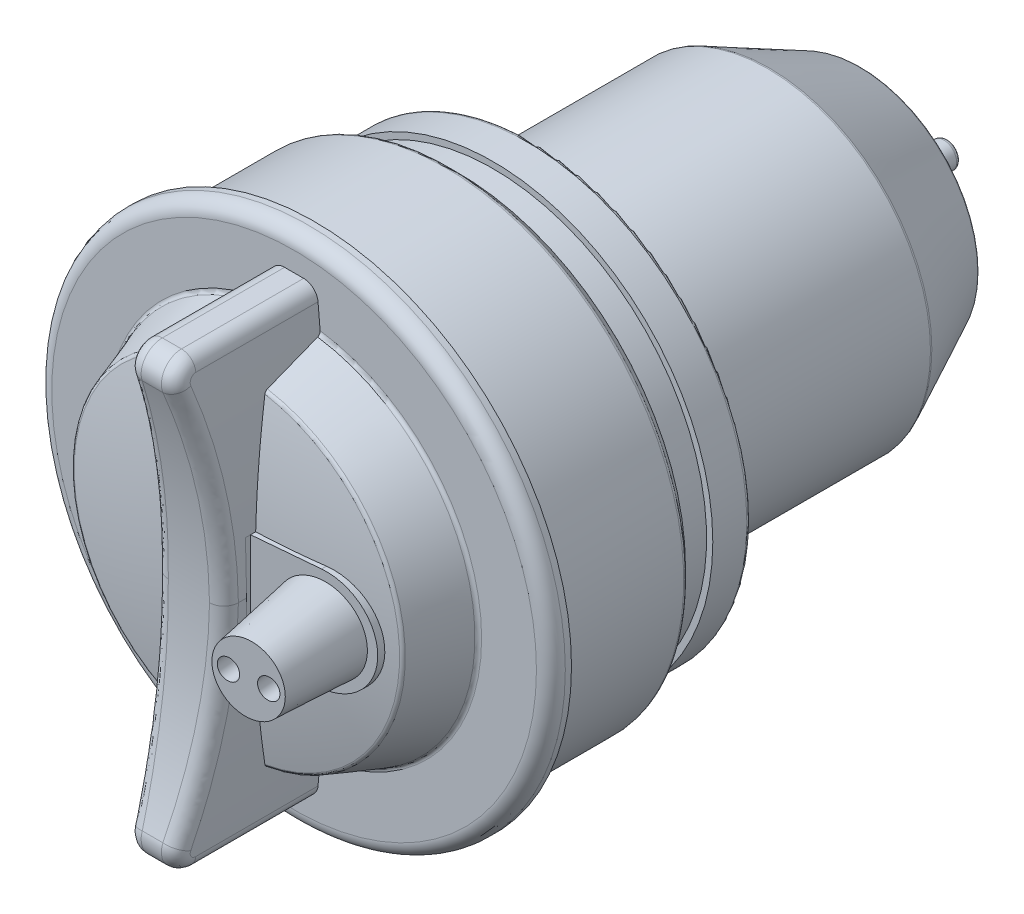
SolidWorks part; units mm, degrees
ref_plane "Front Plane" through (0, 0, 0) normal (0, 0, 1) x (1, 0, 0)
ref_plane "Top Plane" through (0, 0, 0) normal (0, 1, 0) x (1, 0, 0)
ref_plane "Right Plane" through (0, 0, 0) normal (1, 0, 0) x (0, 0, -1)
sketch "Sketch1" plane through (0, 0, 0) normal (0, 0, 1) x (1, 0, 0)
  circle A0 centre (0, 0) radius 20.066
  dimension "D1" = 40.132
extrude "Boss-Extrude1" add sketch "Sketch1" along normal blind 40.64
chamfer "Chamfer1" distance 5.588 distance2 11.43 1 edges at (20.066, 0, 0) first distance on face at (20.066, 0, 0)
sketch "Sketch3" plane through (0, 0, 40.64) normal (0, 0, 1) x (1, 0, 0)
  circle A0 centre (0, 0) radius 26.289
  dimension "D1" = 52.578
extrude "Boss-Extrude2" add sketch "Sketch3" along normal blind 8.89
sketch "Sketch4" plane through (0, 0, 40.64) normal (0, 0, -1) x (-1, 0, 0)
  circle A0 centre (0, 0) radius 24.003
  circle A1 centre (0, 0) radius 20.066
  dimension "D1" = 48.006
  dimension "D2" = 40.132
extrude "Cut-Extrude1" cut sketch "Sketch4" against normal blind 1.778
sketch "Sketch5" plane through (0, 0, 40.64) normal (0, 0, -1) x (-1, 0, 0)
  circle A0 centre (0, 0) radius 27.051
  circle A1 centre (0, 0) radius 26.289
  dimension "D1" = 54.102
extrude "Boss-Extrude3" add sketch "Sketch5" against normal blind 4.699
sketch "Sketch6" plane through (0, 0, 49.53) normal (0, 0, 1) x (1, 0, 0)
  circle A0 centre (0, 0) radius 29.4005
  dimension "D1" = 58.801
extrude "Boss-Extrude4" add sketch "Sketch6" along normal blind 17.78
chamfer "Chamfer2" distance 1.524 angle 45 1 edges at (29.4005, 0, 49.53)
sketch "Sketch8" plane through (0, 0, 67.31) normal (0, 0, 1) x (1, 0, 0)
  circle A0 centre (0, 0) radius 31.623
  dimension "D1" = 63.246
extrude "Boss-Extrude5" add sketch "Sketch8" along normal blind 2.54
fillet "Fillet1" radius 1.778 1 edges at (31.623, 0, 69.85)
sketch "Sketch9" plane through (0, 0, 0) normal (1, 0, 0) x (0, 0, -1)
  line L0 (-69.85, 0) -> (-69.85, -22.733)
  line L1 (-69.85, 31.623) -> (-69.85, -31.623) construction
  line L2 (-69.85, -22.733) -> (-76.835, -20.32)
  line L4 (-78.994, 0) -> (-69.85, 0)
  spline S0 degree 2 poles (-78.994, 0) (-79.1044, -10.2687) (-76.835, -20.32) knots 0 0 0 1 1 1
  dimension "D1" = 22.733
  dimension "D2" = 20.32
  dimension "D3" = 9.144
  dimension "D4" = 6.985
revolve "Revolve1" add sketch "Sketch9" angle 360 about L4
sketch "Sketch10" plane through (0, 0, 69.85) normal (0, 0, 1) x (1, 0, 0)
  line L0 (0, -39.5889) -> (0, 36.9015) construction
  line L1 (-2.794, 27.432) -> (2.794, 27.432)
  line L2 (0, 0) -> (-18.8505, 0) construction
  line L3 (-2.794, -27.432) -> (2.794, -27.432)
  circle A0 centre (0, 0) radius 31.623 construction
  spline S0 degree 2 poles (-4.318, 0) (-4.1228, 13.7514) (-2.794, 27.432) knots 0 0 0 1 1 1
  spline S1 degree 2 poles (-4.318, 0) (-4.1228, -13.7514) (-2.794, -27.432) knots 0 0 0 1 1 1
  spline S2 degree 2 poles (4.318, 0) (4.1228, -13.7514) (2.794, -27.432) knots 0 0 0 1 1 1
  spline S3 degree 2 poles (4.318, 0) (4.1228, 13.7514) (2.794, 27.432) knots 0 0 0 1 1 1
  point P16 (0, 27.432)
  point P17 (0, -27.432)
  dimension "D1" = 4.318
  dimension "D2" = 2.794
  dimension "D3" = 3.556
  dimension "D4" = 27.432
extrude "Boss-Extrude6" add sketch "Sketch10" along normal blind 18.796
sketch "Sketch11" plane through (0, 0, 0) normal (1, 0, 0) x (0, 0, -1)
  line L0 (-88.646, 0) -> (-78.9348, 0) construction
  line L1 (-88.646, -27.432) -> (-69.85, -27.432) construction
  line L2 (-88.646, 0) -> (-88.646, -27.432) construction
  line L3 (-88.646, 27.432) -> (-88.646, -27.432)
  spline S0 degree 2 poles (-88.646, 27.432) (-76.962, 0) (-88.646, -27.432) knots 0 0 0 1 1 1
  dimension "D1" = 5.842
extrude "Cut-Extrude2" cut sketch "Sketch11" against normal mid plane 18.796
fillet "Fillet2" radius 2.54 2 edges at (0, -27.432, 88.646) (0, 27.432, 88.646)
fillet "Fillet3" radius 1.778 12 edges at (-2.794, -27.432, 77.3737) (-2.907, -26.2471, 87.0458) (-2.794, 27.432, 77.3737) (-2.8881, 26.4479, 86.9051) (2.794, -27.432, 77.3737) (2.8881, -26.4479, 86.9051) (2.794, 27.432, 77.3737) (2.907, 26.2471, 87.0458) (-3.72, -15.7702, 84.7347) (-4.1494, 6.8747, 83.1709) (4.1494, -6.8747, 83.1709) (3.72, 15.7702, 84.7347)
fillet "Fillet4" radius 0.508 4 edges at (22.733, 0, 69.85) (-22.733, 0, 69.85) (-20.32, 0, 76.835) (20.32, 0, 76.835)
sketch "Sketch12" plane through (0, 0, 69.85) normal (0, 0, 1) x (1, 0, 0)
  line L0 (12.192, 6.35) -> (1.0967, 6.35)
  line L1 (1.0967, 6.35) -> (1.0967, -6.35)
  line L2 (1.0967, -6.35) -> (12.192, -6.35)
  arc A0 (12.192, -6.35) -> (12.192, 6.35) centre (12.192, 0) ccw
  dimension "D1" = 12.7
  dimension "D2" = 12.192
extrude "Boss-Extrude7" add sketch "Sketch12" along normal blind 10.16
sketch "Sketch13" plane through (0, 0, 0) normal (0, 1, 0) x (1, 0, 0)
  line L0 (4.1673, -80.01) -> (4.1673, -79.3789)
  line L1 (4.1673, -78.7479) -> (4.1673, -80.01) construction
  line L2 (4.1673, -79.3789) -> (19.0286, -78.0506)
  line L3 (19.0286, -78.0506) -> (19.2038, -80.01)
  line L4 (19.2038, -80.01) -> (4.1673, -80.01)
extrude "Cut-Extrude3" cut sketch "Sketch13" against normal mid plane 15.24
sketch "Sketch14" plane through (7.072, 0, 79.1193) normal (0.089, 0, 0.996) x (0.996, 0, -0.089)
  circle A0 centre (5.1404, 0) radius 5.207
  dimension "D1" = 10.414
extrude "Boss-Extrude8" add sketch "Sketch14" along normal blind 9.906 draft 6
sketch "Sketch16" plane through (7.9539, 0, 88.986) normal (0.089, 0, 0.996) x (0.996, 0, -0.089)
  circle A0 centre (2.8544, 0) radius 1.27
  circle A1 centre (7.4264, 0) radius 1.27
  circle A2 centre (5.1404, 0) radius 4.1658 construction
  dimension "D1" = 2.54
  dimension "D2" = 2.54
  dimension "D3" = 4.572
  dimension "D4" = 2.286
extrude "Cut-Extrude4" cut sketch "Sketch16" against normal blind 7.62
sketch "Sketch17" plane through (0, 0, 0) normal (0, 0, -1) x (-1, 0, 0)
  circle A0 centre (0, 0) radius 5.715
  dimension "D1" = 11.43
extrude "Cut-Extrude5" cut sketch "Sketch17" against normal blind 2.032
fillet "Fillet5" radius 0.508 5 edges at (29.4005, 0, 51.054) (27.8765, 0, 49.53) (-27.051, 0, 40.64) (20.066, 0, 11.43) (14.478, 0, 0)
sketch "Sketch18" plane through (0, 0, 0) normal (0, 0, -1) x (-1, 0, 0)
  circle A0 centre (-6.1659, 10.2417) radius 1.27
  circle A1 centre (11.9525, 0.219) radius 1.27
  circle A2 centre (-5.7866, -10.4607) radius 1.27
  point P8 (0, 0)
  dimension "D1" = 3
extrude "Cut-Extrude6" cut sketch "Sketch18" against normal blind 0.508
sketch "Sketch19" plane through (0, 0, 2.032) normal (0, 0, -1) x (-1, 0, 0)
  circle A0 centre (0, 0) radius 1.5875
extrude "Boss-Extrude9" add sketch "Sketch19" along normal blind 12.7
fillet "Fillet6" radius 0.508 1 edges at (-1.5875, 0, -10.668)
